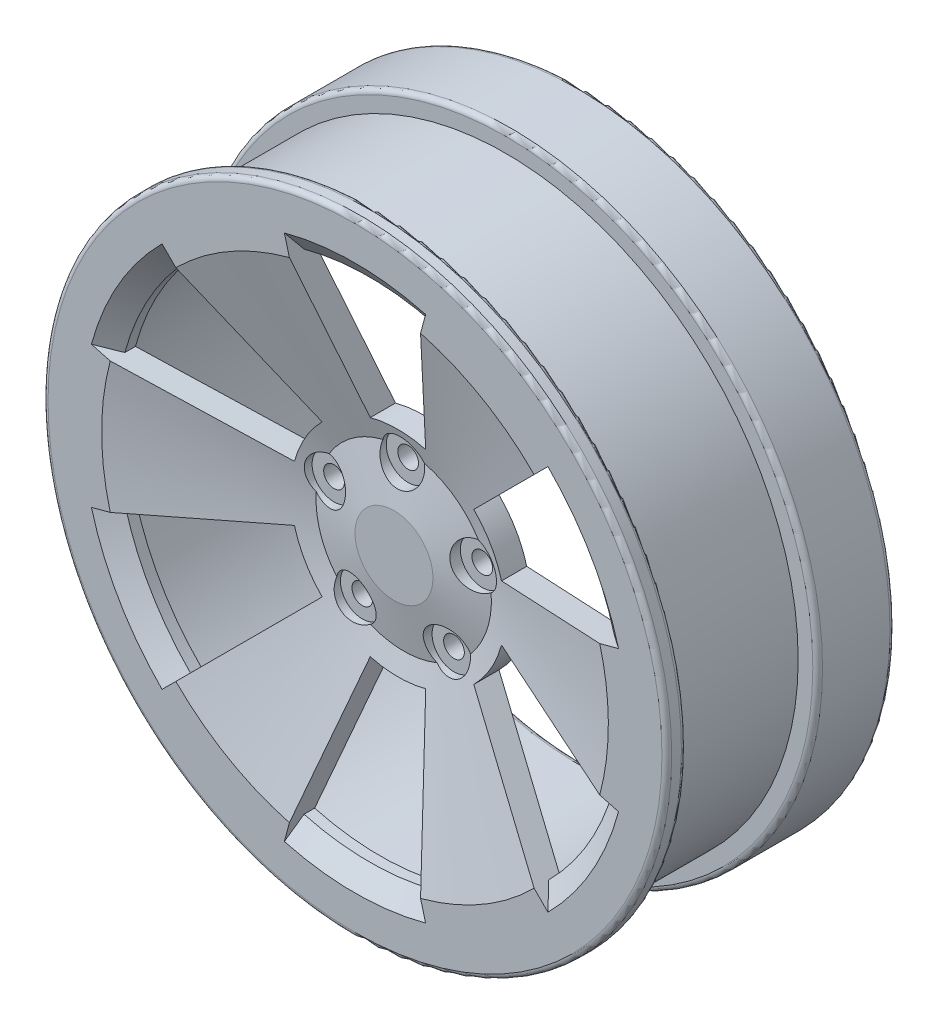
SolidWorks part; units mm, degrees
material "1060 Alloy"
ref_plane "Front Plane" through (0, 0, 0) normal (0, 0, 1) x (1, 0, 0)
ref_plane "Top Plane" through (0, 0, 0) normal (0, 1, 0) x (1, 0, 0)
ref_plane "Right Plane" through (0, 0, 0) normal (1, 0, 0) x (0, 0, -1)
sketch "Sketch2" plane through (0, 0, 0) normal (1, 0, 0) x (0, 0, -1)
  line L0 (0, 0) -> (0, 242.6242) construction
  line L1 (0, 165.1) -> (0, 200.025)
  line L2 (3.175, 203.2) -> (9.525, 203.2)
  line L3 (12.7, 200.025) -> (12.7, 190.5)
  line L4 (12.7, 190.5) -> (98.298, 190.5)
  line L5 (98.298, 190.5) -> (98.298, 200.025)
  line L6 (101.473, 203.2) -> (145.415, 203.2)
  line L7 (148.59, 200.025) -> (148.59, 180.975)
  line L8 (145.415, 177.8) -> (12.7, 177.8)
  line L9 (0, 165.1) -> (31.75, 57.15)
  line L10 (31.75, 57.15) -> (25.4, 25.4)
  line L11 (25.4, 25.4) -> (25.4, 0)
  line L12 (25.4, 0) -> (44.45, 0)
  line L13 (44.45, 0) -> (44.45, 69.85)
  line L14 (44.45, 69.85) -> (12.7, 177.8)
  arc A0 (0, 200.025) -> (3.175, 203.2) centre (3.175, 200.025) cw
  arc A1 (9.525, 203.2) -> (12.7, 200.025) centre (9.525, 200.025) cw
  arc A2 (98.298, 200.025) -> (101.473, 203.2) centre (101.473, 200.025) cw
  arc A3 (145.415, 203.2) -> (148.59, 200.025) centre (145.415, 200.025) cw
  arc A4 (148.59, 180.975) -> (145.415, 177.8) centre (145.415, 180.975) cw
  point P18 (12.7, 195.2625)
  point P26 (34.925, 0)
  dimension "D4" = 3.175
  dimension "D3" = 3.175
  dimension "D5" = 3.175
  dimension "D6" = 3.175
  dimension "D18" = 3.175
  dimension "D1" = 177.8
  dimension "D2" = 12.7
  dimension "D7" = 50.292
  dimension "D8" = 148.59
  dimension "D9" = 12.7
  dimension "D10" = 25.4
  dimension "D11" = 165.1
  dimension "D12" = 25.4
  dimension "D13" = 69.85
  dimension "D14" = 6.35
  dimension "D15" = 31.75
  dimension "D16" = 25.4
  dimension "D17" = 19.05
revolve "Revolve1" add sketch "Sketch2" angle 360 about L12
sketch "Sketch3" plane through (0, 0, 0) normal (0, 0, 1) x (1, 0, 0)
  line L0 (-18.0785, 67.4699) -> (-42.731, 159.4744)
  line L1 (42.731, 159.4744) -> (18.0785, 67.4699)
  line L2 (0, 0) -> (0, 165.1) construction
  circle A0 centre (0, 0) radius 165.1 construction
  arc A2 (18.0785, 67.4699) -> (-18.0785, 67.4699) centre (0, 0) ccw
  arc A3 (42.731, 159.4744) -> (-42.731, 159.4744) centre (0, 0) ccw
  point P1 (0, 165.1)
  dimension "D1" = 69.85
  dimension "D2" = 30
  dimension "D4" = 15
extrude "Cut-Extrude1" cut sketch "Sketch3" against normal through all
pattern_circular "CirPattern1" count 6 over 360 about axis through (0, 0, 0) along (0, 0, 1) of "Cut-Extrude1"
sketch "Sketch6" plane through (0, 0, -25.4) normal (0, 0, 1) x (1, 0, 0)
  line L0 (0, 0) -> (0, 50.8) construction
  circle A0 centre (0, 0) radius 50.8 construction
  dimension "D1" = 101.6
hole_wizard "CBORE for 1/2 Hex Head Bolt2" positions "3DSketch2" profile "Sketch7" counterbore size "1/2" standard "ANSI Inch" end condition through all
sketch3d "3DSketch2"
  circle A0 centre (0, 0, -25.4) radius 50.8 construction
  point P0 (0, 50.8, -25.4)
  point P4 (0, 0, 25.4)
  point P6 (0, 0, 0)
  point P14 (0, 0, 0)
sketch "Sketch7" plane through (0, 50.8, -25.4) normal (1, 0, 0) x (0, -1, 0)
  line L0 (0, 0) -> (0, 123.19)
  line L1 (0, 123.19) -> (6.7462, 123.19)
  line L3 (6.7462, 123.19) -> (6.7462, 9.2456)
  line L4 (14.2875, 9.2456) -> (6.7462, 9.2456)
  line L5 (14.2875, 9.2456) -> (14.2875, 0.7305)
  line L6 (14.2875, 0.7305) -> (14.9225, 0)
  line L7 (14.9225, 0) -> (0, 0)
  line L8 (-14.2875, 0.7305) -> (-14.9225, 0) construction
  line L11 (0, -6.35) -> (0, 107.95) construction
  dimension "Thru Hole Dia." = 13.4925
  dimension "Thru Hole Depth" = 123.19
  dimension "C'Bore Dia." = 28.575
  dimension "C'Bore Depth" = 9.2456
  dimension "Near C'Sink Dia." = 29.845
  dimension "Near C'Sink Angle" = 82
pattern_circular "CirPattern2" count 5 over 360 about axis through (0, 0, 0) along (0, 0, 1) of "CBORE for 1/2 Hex Head Bolt2"
chamfer "Chamfer1" distance 12.7 angle 36.87 1 edges at (142.9808, 82.55, 0) first distance on face at (0, 0, 0)
chamfer "Chamfer7" distance 12.7 angle 36.87 5 edges at (142.9808, -82.55, 0) (0, -165.1, 0) (-142.9808, -82.55, 0) (-142.9808, 82.55, 0) (0, 165.1, 0) first distance on face at (21.2743, 12.2827, 0)
equation "\"R\"=0.125"
equation "\"D4@Sketch2\"=\"R\""
equation "\"D3@Sketch2\"=\"R\""
equation "\"D5@Sketch2\"=\"R\""
equation "\"D6@Sketch2\"=\"R\""
equation "\"A\"=5.85"
equation "\"D8@Sketch2\"=\"A\""
equation "\"B\"=1.98"
equation "\"D7@Sketch2\"=\"B\""
equation "\"D18@Sketch2\"=\"R\""
